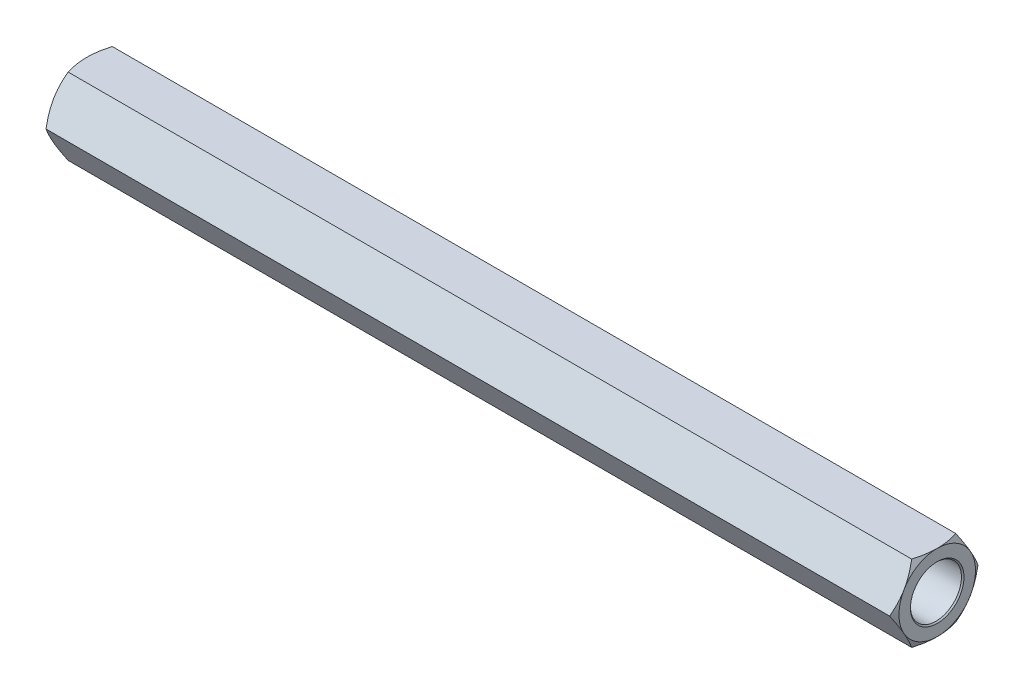
SolidWorks part; units mm, degrees
material "6061-T6 (SS)"
ref_plane "Front Plane" through (0, 0, 0) normal (0, 0, 1) x (1, 0, 0)
ref_plane "Top Plane" through (0, 0, 0) normal (0, 1, 0) x (1, 0, 0)
ref_plane "Right Plane" through (0, 0, 0) normal (1, 0, 0) x (0, 0, -1)
sketch "Sketch1" plane through (0, 0, 0) normal (0, 0, 1) x (1, 0, 0)
  line L0 (0, 0) -> (50, 0) construction
  line L1 (0, 2.25) -> (0, -2.25) construction
  line L2 (0, 1.5) -> (6.3, 1.5) construction
  line L3 (0, 1.5) -> (-0.5, 1.5) construction
  line L4 (0, 2.25) -> (50, 2.25) construction
  point P6 (0, 0)
  dimension "Hex" = 4.5
  dimension "Pitch" = 0.5
  dimension "Thread Length" = 6.3
  dimension "Thread OD" = 3
  dimension "Length" = 50
sketch "Sketch2" plane through (0, 0, 0) normal (1, 0, 0) x (0, 0, -1)
  line L0 (0, 0) -> (-1.0607, -1.0607) construction
  line L1 (1.299, 2.25) -> (-1.299, 2.25)
  line L2 (-1.299, 2.25) -> (-2.5981, 0)
  line L3 (-2.5981, 0) -> (-1.299, -2.25)
  line L4 (-1.299, -2.25) -> (1.299, -2.25)
  line L5 (1.299, -2.25) -> (2.5981, 0)
  line L6 (2.5981, 0) -> (1.299, 2.25)
  circle A0 centre (0, 0) radius 2.25 construction
  circle A1 centre (0, 0) radius 1.5 construction
  dimension "D1" = 45
extrude "Boss-Extrude1" add sketch "Sketch2" along normal up to vertex (50 mm away) up to point (50, 0, 0)
sketch "Sketch3" plane through (0, 0, 0) normal (0, 0, 1) x (1, 0, 0)
  line L0 (0, 1.575) -> (0.075, 1.5)
  line L1 (0, 0) -> (6.3, 0)
  line L2 (0, 0) -> (0, 1.575)
  line L3 (0.075, 1.5) -> (6.3, 1.5)
  line L4 (6.3, 0) -> (6.3, 1.5)
  line L5 (50, 0) -> (43.7, 0)
  line L8 (43.7, 0) -> (43.7, 1.5)
  line L9 (0, 2.25) -> (0, -2.25) construction
  line L13 (0, 0) -> (50, 0) construction
  line L14 (43.7, 1.5) -> (49.925, 1.5)
  line L15 (49.925, 1.5) -> (50, 1.575)
  line L16 (50, 2.25) -> (50, 0) construction
  line L17 (50, 1.575) -> (50, 0)
  dimension "D1" = 3.15
  dimension "D2" = 45
revolve "Cut-Revolve1" cut sketch "Sketch3" angle 360 about L13
sketch "Sketch4" plane through (0, 0, 0) normal (-1, 0, 0) x (0, 0, 1)
  circle A0 centre (0, 0) radius 2.25
  circle A1 centre (0, 0) radius 2.25 construction
extrude "Cut-Extrude1" cut sketch "Sketch4" against normal through all draft 60 flip side to cut
sketch "Sketch5" plane through (50, 0, 0) normal (1, 0, 0) x (0, 0, -1)
  circle A0 centre (0, 0) radius 2.25
  circle A1 centre (0, 0) radius 2.25 construction
extrude "Cut-Extrude2" cut sketch "Sketch5" against normal through all draft 60 flip side to cut
ref_axis "Center Axis 1" through (0, 0, 0) along (1, 0, 0)
sketch "Sketch6" [suppressed] plane through (0, 0, 0) normal (0, 0, 1) x (1, 0, 0)
  line L0 (-0.4278, 1.5) -> (-0.2139, 1.1295) construction
  line L1 (-0.2139, 1.1295) -> (0, 1.5) construction
  line L2 (0, 1.5) -> (-0.4278, 1.5) construction
  line L3 (0, 1.5) -> (-0.5, 1.5) construction
  line L5 (-0.4278, 1.5) -> (-0.4639, 1.5625) construction
  line L6 (-0.4639, 1.5625) -> (0.0361, 1.5625) construction
  line L7 (0.0361, 1.5625) -> (0, 1.5) construction
  line L8 (-0.2452, 1.1836) -> (-0.1827, 1.1836) construction
  line L9 (-0.2139, 1.5) -> (-0.2139, 1.5625) construction
  line L10 (-0.4459, 1.5312) -> (0.018, 1.5312)
  line L11 (0.018, 1.5312) -> (-0.1827, 1.1836)
  line L12 (-0.1827, 1.1836) -> (-0.2452, 1.1836)
  line L13 (-0.2452, 1.1836) -> (-0.4459, 1.5312)
  dimension "D1" = 0.0625
sketch "Sketch7" [suppressed] plane through (0, 0, 0) normal (-1, 0, 0) x (0, 0, 1)
  line L0 (0, 2.25) -> (0, -2.25) construction
  circle A0 centre (0, 0) radius 1.5
curve "Helix/Spiral1" [suppressed] pitch 0.5 height 6.8 turns 13.6
sweep "Sweep1" [suppressed] add profiles "Sketch6" path "Helix/Spiral1"
pattern_linear "LPattern1" [suppressed] count 2 spacing 43.7 along (1, 0, 0)
combine bodies "Combine1" [suppressed] operation type add bodies to combine 107 108 109
sketch "Sketch8" [suppressed] plane through (0, 0, 0) normal (-1, 0, 0) x (0, 0, 1)
  circle A0 centre (0, 0) radius 1.575
extrude "Cut-Extrude3" [suppressed] cut sketch "Sketch8" against normal through all draft 45 and the other way through all draft 45
sketch "Sketch9" [suppressed] plane through (50, 0, 0) normal (1, 0, 0) x (0, 0, -1)
  circle A0 centre (0, 0) radius 1.575
  circle A1 centre (0, 0) radius 1.575 construction
extrude "Cut-Extrude4" [suppressed] cut sketch "Sketch9" against normal through all draft 45 and the other way through all draft 45
equation "\"D1@Sketch3\"=\"Thread OD@Sketch1\"*1.05"
equation "\"D1@Sketch6\"=\"Pitch@Sketch1\"/8"
equation "\"D4@Helix/Spiral1\"=\"Pitch@Sketch1\""
equation "\"D3@Helix/Spiral1\"=\"Pitch@Sketch1\"+\"Thread Length@Sketch1\""
equation "\"D3@LPattern1\"=\"Length@Sketch1\"-\"Thread Length@Sketch1\""
